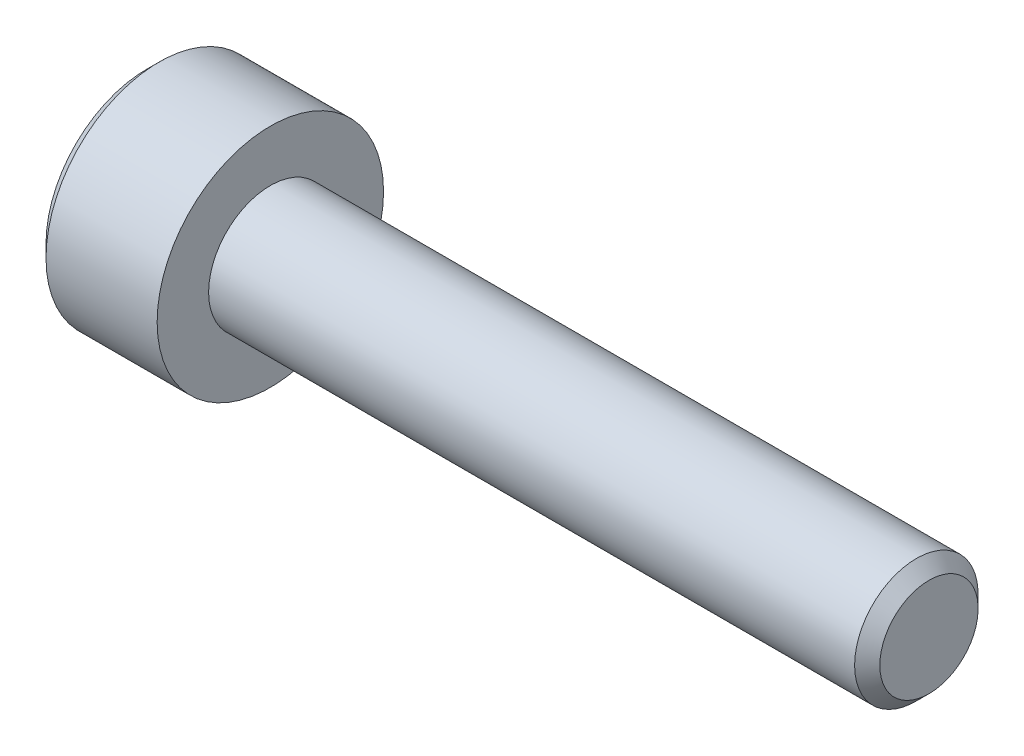
SolidWorks part; units mm, degrees
ref_plane "Front Plane" through (0, 0, 0) normal (0, 0, 1) x (1, 0, 0)
ref_plane "Top Plane" through (0, 0, 0) normal (0, 1, 0) x (1, 0, 0)
ref_plane "Right Plane" through (0, 0, 0) normal (1, 0, 0) x (0, 0, -1)
ref_plane "Plane1" through (1, 0, 0) normal (1, 0, 0) x (0, 0, -1)
ref_axis "Axis_X" through (-3.95, 0, 0) along (1, 0, 0)
ref_axis "Axis_Y" through (0, 3.025, 0) along (0, -1, 0)
ref_axis "Axis_Z" through (0, 0, -3.025) along (0, 0, 1)
sketch "Sketch1" plane through (0, 0, 0) normal (0, 0, 1) x (1, 0, 0)
  line L0 (-3, 0) -> (16, 0)
  line L1 (16, 0) -> (16, -1.1935)
  line L2 (16, -1.1935) -> (15.6935, -1.5)
  line L3 (15.6935, -1.5) -> (0, -1.5)
  line L4 (0, -1.5) -> (0, -2.75)
  line L5 (0, -2.75) -> (-2.7, -2.75)
  line L6 (-2.7, -2.75) -> (-3, -2.45)
  line L7 (-3, -2.45) -> (-3, 0)
  line L8 (0, 0) -> (-3, 0) construction
  line L9 (16, 1.1935) -> (15.6935, 1.5) construction
  line L10 (-3, 2.45) -> (-2.7, 2.75) construction
  point P16 (15.5, -1.5)
  dimension "A" = 5.5
  dimension "E" = 3
  dimension "MSM_1" = 2.387
  dimension "MSM_2" = 45
  dimension "MSM_3" = 0.3
  dimension "L" = 16
  dimension "Pitch_1" = 0.5
revolve "Revolve1" add sketch "Sketch1" angle 360 about axis through (-3.95, 0, 0) along (1, 0, 0)
sketch "Sketch2" plane through (-3, 0, 0) normal (-1, 0, 0) x (0, 0, 1)
  line L1 (0, 1.4434) -> (-1.25, 0.7217)
  line L2 (-1.25, 0.7217) -> (-1.25, -0.7217)
  line L3 (-1.25, -0.7217) -> (0, -1.4434)
  line L4 (0, -1.4434) -> (1.25, -0.7217)
  line L5 (1.25, -0.7217) -> (1.25, 0.7217)
  line L6 (1.25, 0.7217) -> (0, 1.4434)
  circle A0 centre (0, 0) radius 1.25 construction
  dimension "B" = 2.5
extrude "Cut-Extrude1" cut sketch "Sketch2" against normal blind 1.5
ref_plane "Dim. B_s" through (16, 0, 0) normal (1, 0, 0) x (0, 0, -1)
sketch "Sketch3" plane through (0, 0, 0) normal (0, 0, 1) x (1, 0, 0)
  line L0 (0, 0) -> (16, 0) construction
  line L1 (16, -1.3128) -> (16, 1.3128) construction
  line L3 (15.99, 1.5) -> (16, 1.5)
  line L5 (15.99, 1.5) -> (15.99, 1.49)
  line L6 (15.99, 1.49) -> (16, 1.49)
  line L7 (16, 1.5) -> (16, 1.49)
  line L8 (13, 1.5) -> (13.01, 1.5)
  line L9 (13, 1.5) -> (13, 1.49)
  line L10 (13, 1.49) -> (13.01, 1.49)
  line L11 (13.01, 1.5) -> (13.01, 1.49)
  dimension "MSM_5" = 0.01
  dimension "A_s" = 3
revolve "Cut-Revolve1" [suppressed] cut sketch "Sketch3" angle 360 about L0
equation "\"Factor\"= 1.082532"
equation "\"ATD_1\"= 4.134"
equation "\"L_s\"= 10"
equation "\"L_s\"= IIF ( ( \"M\" = 12 and \"L\" > 50 ) , 36 , IIF ( ( \"M\" = 10 and \"L\" > 40 ) , 32 , IIF ( ( \"M\" = 8 and \"L\" > 35 ) , 28 , IIF ( ( \"M\" = 6 and \"L\" > 30 ) , 24 , IIF ( ( \"M\" = 5 and \"L\" > 25 ) , 22 , IIF ( ( \"M\" = 4 and \"L\" > 25 ) , 20 , IIF ( ( \"M\" = 3 and \"L\" > 20 ) , 18 , \"L\" ) ) ) ) ) ) )"
equation "\"A\"= IIF ( \"M\" = 12 , 18 , IIF ( \"M\" = 10 , 16 , IIF ( \"M\" = 8 , 13 , IIF ( \"M\" = 6 , 10 , IIF ( \"M\" = 5 , 8.5 , IIF ( \"M\" = 4 , 7 , IIF ( \"M\" = 3 , 5.5 , IIF ( \"M\" = 2.6 or \"M\" = 2.5 , 4.5 , 3.8 ) ) ) ) ) ) ) )"
equation "\"E\"= \"M\""
equation "\"B\"= IIF ( \"M\" = 12 , 10 , IIF ( \"M\" = 10 , 8 , IIF ( \"M\" = 8 , 6 , IIF ( \"M\" = 6 , 5 , IIF ( \"M\" = 5 , 4 , IIF ( \"M\" = 4 , 3 , IIF ( \"M\" = 3 , 2.5 , IIF ( \"M\" = 2.6 or \"M\" = 2.5 , 2 , 1.5 ) ) ) ) ) ) ) )"
equation "\"MSM_4\"= \"M\" * 0.5"
equation "\"MSM_1\"= IIF ( \"M\" = 12 , 9.853 , IIF ( \"M\" = 10 , 8.16 , IIF ( \"M\" = 8 , 6.466 , IIF ( \"M\" = 6 , 4.773 , IIF ( \"M\" = 5 , 4.019 , IIF ( \"M\" = 4 , 3.141 , IIF ( \"M\" = 3 , 2.387 , IIF ( \"M\" = 2.6 , 2.048 , IIF ( \"M\" = 2.5 , 1.948 , 1.509 ) ) ) ) ) ) ) ) )"
equation "\"MSM_2\"= 45"
equation "\"MSM_3\"= IIF ( \"M\" = 2.6 , 0.26 , \"E\" * 0.1 )"
equation "\"Thread1\" = IIF ( ( ( \"M\" = 12 ) and ( \"L\" > 50 ) ) or ( ( \"M\" = 10 ) and ( \"L\" > 40 ) ) or ( ( \"M\" = 8 ) and ( \"L\" > 35 ) ) or ( ( \"M\" = 6 ) and ( \"L\" > 30 ) ) or ( ( \"M\" = 5 ) and ( \"L\" > 25 ) ) or ( ( \"M\" = 4 ) and ( \"L\" > 25 ) ) or ( \"M\" = 3 ) and ( \"L\" > 2 ) , \"suppressed\" , \"unsuppressed\" )"
equation "\"Thread2\" = IIF ( ( ( \"M\" = 12 ) and ( \"L\" > 50 ) ) or ( ( \"M\" = 10 ) and ( \"L\" > 40 ) ) or ( ( \"M\" = 8 ) and ( \"L\" > 35 ) ) or ( ( \"M\" = 6 ) and ( \"L\" > 30 ) ) or ( ( \"M\" = 5 ) and ( \"L\" > 25 ) ) or ( ( \"M\" = 4 ) and ( \"L\" > 25 ) ) or ( \"M\" = 3 ) and ( \"L\" > 2 ) , \"unsuppressed\" , \"suppressed\" )"
equation "\"MSM_5\"= 0.01"
equation "\"Cut-Revolve1\"= IIF ( \"TYP\" = 2 , \"unsuppressed\" , \"suppressed\" )"
equation "\"Pitch_1\"= IIF ( \"M\" = 12 , 1.75 , IIF ( \"M\" = 10 , 1.5 , IIF ( \"M\" = 8 , 1.25 , IIF ( \"M\" = 6 , 1 , IIF ( \"M\" = 5 , 0.8 , IIF ( \"M\" = 4 , 0.7 , IIF ( \"M\" = 3 , 0.5 , IIF ( \"M\" = 2.6 or \"M\" = 2.5 , 0.45 , 0.4 ) ) ) ) ) ) ) )"
equation "\"ATD_2\"= round ( \"M\" - \"Factor\" * \"Pitch_1\" , 3 )"
